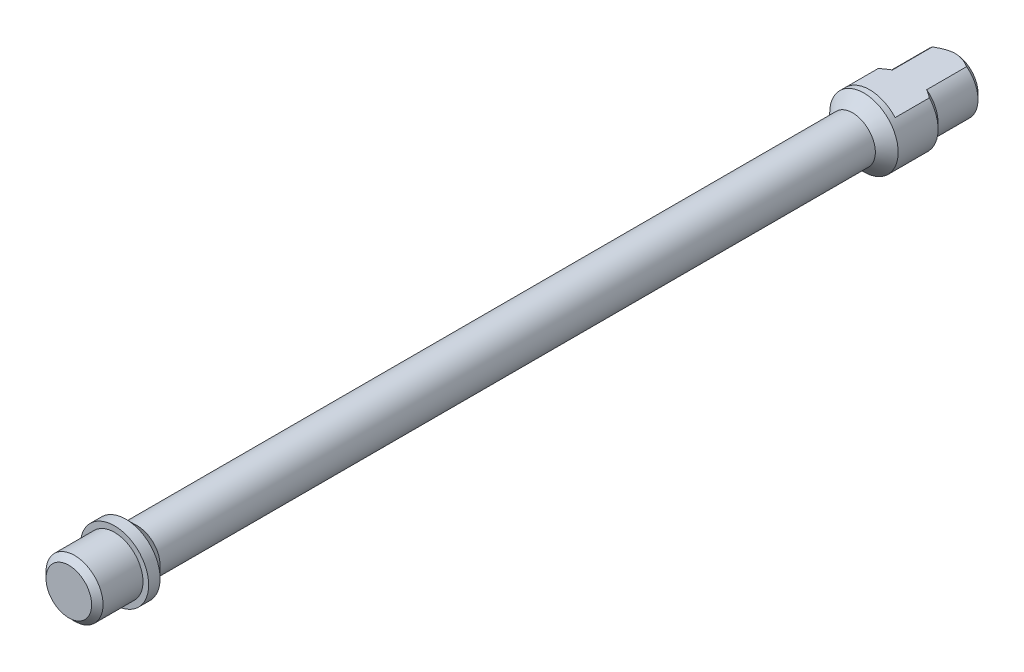
SolidWorks part; units mm, degrees
material "2A12"
ref_plane "前视基准面" through (0, 0, 0) normal (0, 0, 1) x (1, 0, 0)
ref_plane "上视基准面" through (0, 0, 0) normal (0, 1, 0) x (1, 0, 0)
ref_plane "右视基准面" through (0, 0, 0) normal (1, 0, 0) x (0, 0, -1)
sketch "草图1" plane through (0, 0, 0) normal (0, 0, 1) x (1, 0, 0)
  circle A0 centre (0, 0) radius 2
  dimension "D1" = 4
extrude "拉伸1" add sketch "草图1" along normal mid plane 64.7
sketch "草图2" plane through (0, 0, 32.35) normal (0, 0, 1) x (1, 0, 0)
  circle A0 centre (0, 0) radius 3
  dimension "D1" = 6
extrude "拉伸2" add sketch "草图2" along normal blind 1
sketch "草图3" plane through (0, 0, 33.35) normal (0, 0, 1) x (1, 0, 0)
  circle A0 centre (0, 0) radius 2.5
  dimension "D1" = 5
extrude "拉伸3" add sketch "草图3" along normal blind 4
sketch "草图4" plane through (0, 0, -32.35) normal (0, 0, -1) x (-1, 0, 0)
  circle A0 centre (0, 0) radius 3
  dimension "D1" = 6
extrude "拉伸4" add sketch "草图4" along normal blind 4
sketch "草图5" plane through (0, 0, -36.35) normal (0, 0, -1) x (-1, 0, 0)
  circle A0 centre (0, 0) radius 2.5
  dimension "D1" = 5
extrude "拉伸5" add sketch "草图5" along normal blind 4
chamfer "倒角1" distance 0.5 angle 45 2 edges at (-2.5, 0, -40.35) (2.5, 0, 37.35)
chamfer "倒角2" distance 0.5 angle 45 1 edges at (-3, 0, -36.35)
sketch "草图6" plane through (0, 0, -40.35) normal (0, 0, -1) x (-1, 0, 0)
  line L0 (0, 0) -> (0, 2) construction
  line L1 (-3, 5) -> (3, 5)
  line L2 (-3, 5) -> (-3, 2)
  line L3 (-3, 2) -> (3, 2)
  line L4 (3, 5) -> (3, 2)
  dimension "D1" = 2
  dimension "D2" = 3
  dimension "D3" = 6
extrude "拉伸6" cut sketch "草图6" against normal blind 7.5
chamfer "Chamfer1" distance 1 angle 45 2 edges at (-2, 0, -32.35) (2, 0, 32.35)
